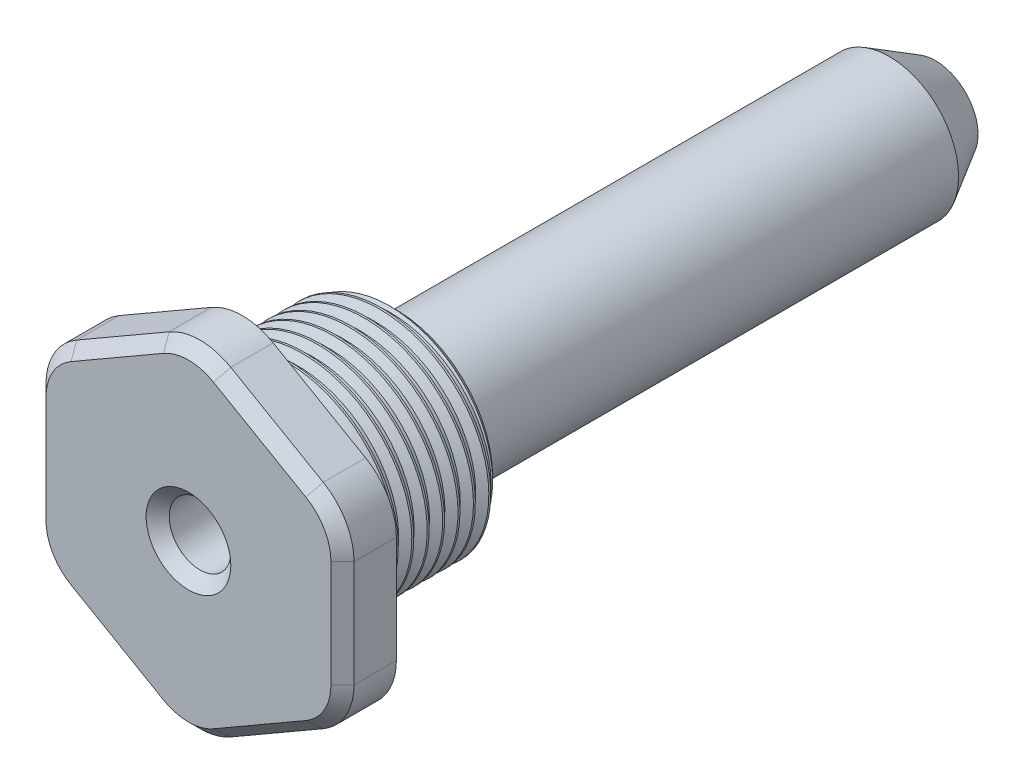
SolidWorks part; units mm, degrees
ref_plane "Front Plane" through (0, 0, 0) normal (0, 0, 1) x (1, 0, 0)
ref_plane "Top Plane" through (0, 0, 0) normal (0, 1, 0) x (1, 0, 0)
ref_plane "Right Plane" through (0, 0, 0) normal (1, 0, 0) x (0, 0, -1)
sketch "Sketch1" plane through (0, 0, 0) normal (0, 0, 1) x (1, 0, 0)
  circle A0 centre (0, 0) radius 7
  dimension "D1" = 14
extrude "Boss-Extrude1" add sketch "Sketch1" along normal blind 10
chamfer "Chamfer1" distance 0.75 angle 45 1 edges at (7, 0, 0)
sketch "Sketch2" plane through (0, 0, 10) normal (0, 0, 1) x (1, 0, 0)
  circle A0 centre (0, 0) radius 7 construction
  circle A1 centre (0, 0) radius 7
curve "Helix/Spiral1" pitch 1 height 11 radius 7 centre (0, 0, 10) axis (0, 0, -1) start towards (1, 0, 0)
sketch "Sketch3" plane through (0, 0, 0) normal (0, 1, 0) x (1, 0, 0)
  line L0 (6.2422, -10.4375) -> (7.1083, -10.4375) construction
  line L1 (7.1083, -9.9375) -> (6.2422, -9.4375) construction
  line L2 (6.2422, -9.4375) -> (6.2422, -11.4375) construction
  line L3 (6.2422, -10.4375) -> (7.1083, -9.9375) construction
  line L4 (7.1083, -10.9375) -> (6.2422, -11.4375) construction
  line L5 (6.2422, -10.4375) -> (7.1083, -10.9375) construction
  line L6 (7, -10.875) -> (7, -11) construction
  line L7 (6.4587, -10.3125) -> (6.4587, -10.5625)
  line L8 (6.4587, -10.5625) -> (7, -10.875)
  line L9 (7, -10.875) -> (7, -10)
  line L10 (7, -10) -> (6.4587, -10.3125)
  circle A0 centre (6.5309, -9.9375) radius 0.2887 construction
  dimension "D1" = 1
  dimension "D2" = 0.125
  dimension "D3" = 0.25
sweep "Cut-Sweep1" cut profiles "Sketch3" path "Helix/Spiral1"
sketch "Sketch4" plane through (0, 0, 10) normal (0, 0, 1) x (1, 0, 0)
  line L1 (0, 11.547) -> (-10, 5.7735)
  line L2 (-10, 5.7735) -> (-10, -5.7735)
  line L3 (-10, -5.7735) -> (0, -11.547)
  line L4 (0, -11.547) -> (10, -5.7735)
  line L5 (10, -5.7735) -> (10, 5.7735)
  line L6 (10, 5.7735) -> (0, 11.547)
  circle A0 centre (0, 0) radius 10 construction
  dimension "D1" = 20
extrude "Boss-Extrude2" add sketch "Sketch4" along normal blind 3.5
fillet "Fillet1" radius 4 6 edges at (10, -5.7735, 11.75) (0, -11.547, 11.75) (-10, -5.7735, 11.75) (-10, 5.7735, 11.75) (0, 11.547, 11.75) (10, 5.7735, 11.75)
chamfer "Chamfer3" distance 0.75 angle 45 12 edges at (0, -10.9282, 13.5) (-5, -8.6603, 13.5) (-9.4641, -5.4641, 13.5) (-10, 0, 13.5) (-9.4641, 5.4641, 13.5) (-5, 8.6603, 13.5) (0, 10.9282, 13.5) (5, 8.6603, 13.5) (9.4641, 5.4641, 13.5) (10, 0, 13.5) (9.4641, -5.4641, 13.5) (5, -8.6603, 13.5)
sketch "Sketch5" plane through (0, 0, 0) normal (0, 0, -1) x (-1, 0, 0)
  circle A0 centre (0, 0) radius 4.5
  dimension "D1" = 9
extrude "Boss-Extrude3" add sketch "Sketch5" along normal blind 35
fillet "Fillet2" radius 0.5 1 edges at (4.5, 0, 0)
sketch "Sketch6" plane through (0, 0, 13.5) normal (0, 0, 1) x (1, 0, 0)
  circle A0 centre (0, 0) radius 2
  dimension "D1" = 4
extrude "Cut-Extrude1" cut sketch "Sketch6" against normal blind 30
chamfer "Chamfer4" distance 3.4 angle 30 1 edges at (2, 0, -16.5) first distance on face at (2, 0, -16.5)
chamfer "Chamfer5" distance 3 angle 30 1 edges at (-4.5, 0, -35) first distance on face at (4.5, 0, -0.5)
chamfer "Chamfer6" distance 0.75 angle 45 1 edges at (2, 0, 13.5)
equation "\"D2@Sketch3\"=1/8"
equation "\"D3@Sketch3\"=1/4"
